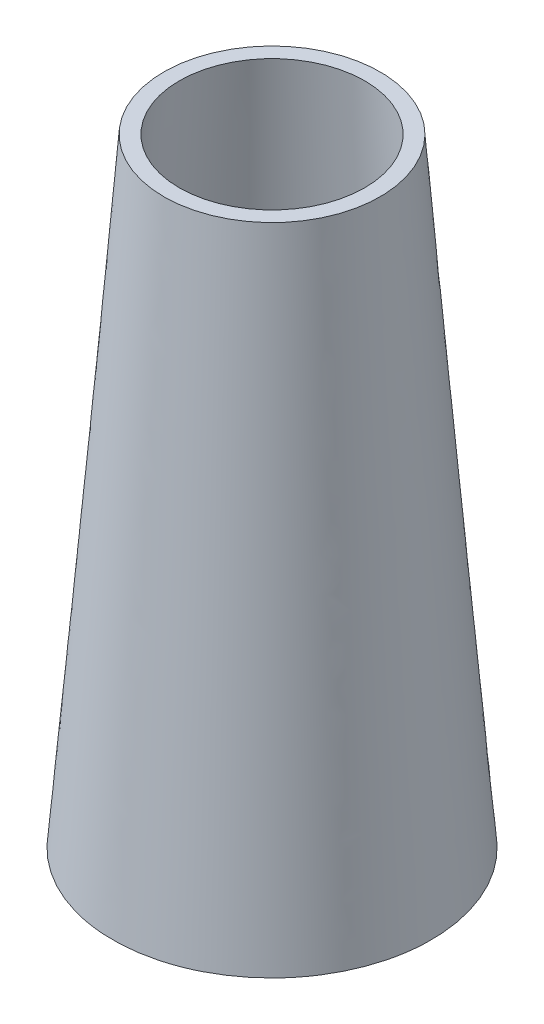
SolidWorks part; units mm, degrees
ref_plane "Front Plane" through (0, 0, 0) normal (0, 0, 1) x (1, 0, 0)
ref_plane "Top Plane" through (0, 0, 0) normal (0, 1, 0) x (1, 0, 0)
ref_plane "Right Plane" through (0, 0, 0) normal (1, 0, 0) x (0, 0, -1)
sketch "Sketch1" plane through (0, 0, 0) normal (0, 1, 0) x (1, 0, 0)
  circle A0 centre (0, 0) radius 5.15
  dimension "D1" = 10.3
ref_plane "Plane1" through (0, 20, 0) normal (0, 1, 0) x (1, 0, 0)
sketch "Sketch2" plane through (0, 20, 0) normal (0, 1, 0) x (1, 0, 0)
  circle A0 centre (0, 0) radius 3.5
  dimension "D1" = 7
loft "Loft1" add profiles "Sketch2", "Sketch1" connector at (-1.4902, 20, -3.1669) connector at (-3.0323, 0, -4.1626)
sketch "Sketch3" plane through (0, 20, 0) normal (0, 1, 0) x (1, 0, 0)
  line L0 (0, 3) -> (0, 3.5) construction
  circle A0 centre (0, 0) radius 3
  circle A1 centre (0, 0) radius 3.5 construction
  dimension "D1" = 0.5
sketch "Sketch4" plane through (0, 0, 0) normal (0, -1, 0) x (1, 0, 0)
  line L0 (0, 4.65) -> (0, 5.15) construction
  circle A0 centre (0, 0) radius 4.65
  circle A1 centre (0, 0) radius 5.15 construction
  dimension "D1" = 0.5
loft "Cut-Loft1" cut profiles "Sketch3", "Sketch4" connector at (-0.6948, 20, -2.9184) connector at (-0.834, 0, -4.5746)
